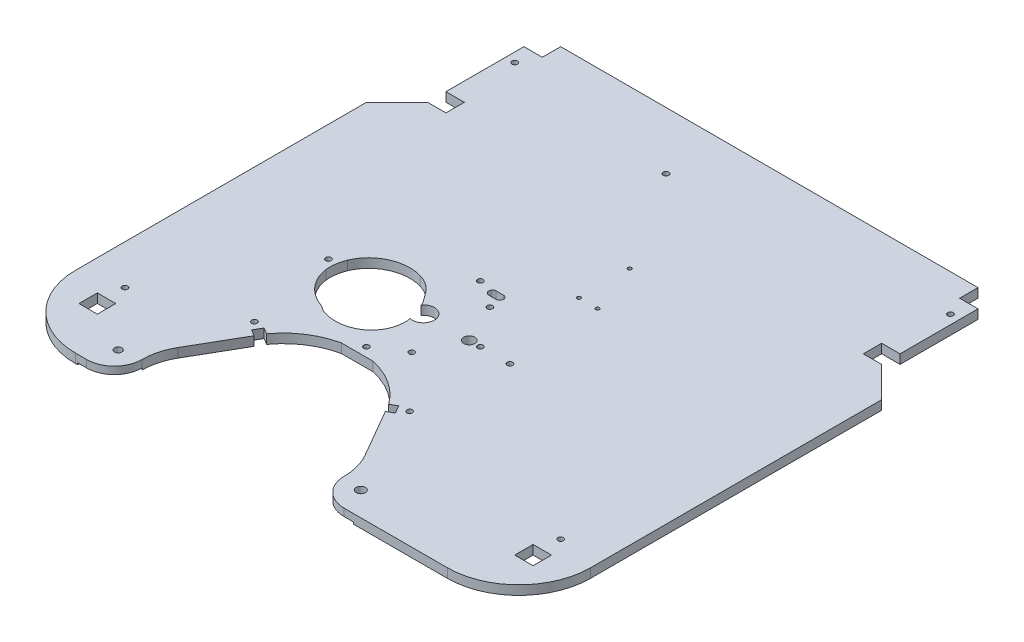
SolidWorks part; units mm, degrees
material "ABS PC"
ref_plane "Plan de face" through (0, 0, 0) normal (0, 0, 1) x (1, 0, 0)
ref_plane "Plan de dessus" through (0, 0, 0) normal (0, 1, 0) x (1, 0, 0)
ref_plane "Plan de droite" through (0, 0, 0) normal (1, 0, 0) x (0, 0, -1)
sketch "Esquisse1" plane through (0, 0, 0) normal (0, 1, 0) x (1, 0, 0)
  line L1 (-140.1, 31.2) -> (140.1, 31.2)
  line L2 (-140.1, 31.2) -> (-140.1, -245.0829)
  line L3 (-140.1, -245.0829) -> (140.1, -245.0829)
  line L4 (140.1, 31.2) -> (140.1, -245.0829)
  line L5 (45, -245.0829) -> (50, -245.0829) construction
  line L6 (-114.5, 31.2) -> (114.5, 31.2) construction
  line L7 (140.1, -4) -> (140.1, 4) construction
  line L8 (-140.1, 4) -> (-140.1, -4) construction
extrude "Boss.-Extru.1" add sketch "Esquisse1" along normal blind 5
sketch "Esquisse2" plane through (0, 0, 0) normal (0, 1, 0) x (1, 0, 0)
  line L3 (-58.1815, -184) -> (-61.6457, -182)
  line L4 (-61.6457, -182) -> (-64.1457, -186.3301)
  line L5 (-64.1457, -186.3301) -> (-60.6815, -188.3301)
  line L7 (-25, -132) -> (-25, -245.0829) construction
  line L8 (-58.1815, -184) -> (-60.6815, -188.3301) construction
  line L9 (-62.6323, -132) -> (62.6323, -132) construction
  line L10 (-25, -62.6323) -> (-25, 62.6323) construction
  line L11 (-60.6815, -188.3301) -> (-75.8539, -214.6094)
  line L13 (-58.1815, -184) -> (-54.7174, -186) construction
  line L14 (-25, -168.25) -> (-25, -231.25) construction
  line L16 (140.1, -245.0829) -> (-140.1, -245.0829) construction
  line L17 (-140.1, -245.0829) -> (140.1, -245.0829) construction
  line L18 (8.1815, -184) -> (4.7174, -186) construction
  line L20 (8.1815, -184) -> (10.6815, -188.3301) construction
  line L21 (10.6815, -188.3301) -> (25.8539, -214.6094)
  line L22 (14.1457, -186.3301) -> (10.6815, -188.3301)
  line L23 (11.6457, -182) -> (14.1457, -186.3301)
  line L24 (8.1815, -184) -> (11.6457, -182)
  line L25 (-62.8957, -184.1651) -> (-67.2258, -181.6651) construction
  line L26 (-95, -245.0829) -> (45, -245.0829)
  arc A0 (-95, -245.0829) -> (-86.2863, -217.8734) centre (-95, -230.0829) ccw construction
  arc A1 (8.1815, -184) -> (-58.1815, -184) centre (-25, -208.0829) ccw
  arc A2 (-95, -245.0829) -> (-80, -230.0829) centre (-95, -230.0829) ccw
  arc A4 (-80, -230.0829) -> (-75.8539, -214.6094) centre (-49.0531, -230.0829) cw
  arc A5 (30, -230.0829) -> (25.8539, -214.6094) centre (-0.9469, -230.0829) ccw
  arc A6 (45, -245.0829) -> (30, -230.0829) centre (45, -230.0829) cw
  circle A8 centre (-67.2258, -181.6651) radius 1.5
  circle A10 centre (17.2258, -181.6651) radius 1.5
  dimension "D4" = 41
  dimension "D8" = 5
  dimension "D9" = 3
  dimension "D1" = 4
  dimension "D2" = 52
  dimension "D3" = 37
  dimension "D5" = 90
  dimension "D6" = 5
  dimension "D7" = 30
extrude "Enlèv. mat.-Extru.2" cut sketch "Esquisse2" along normal through all
sketch "Esquisse3" plane through (0, 5, 0) normal (0, 1, 0) x (1, 0, 0)
  line L0 (-30.2198, -127.0596) -> (-26.1089, -139.1328)
  spline S0 degree 3 poles (-37.7914, -122.1402) (-38.0734, -121.8243) (-38.3657, -121.5165) (-38.9965, -120.9381) (-39.3221, -120.6716) (-39.9982, -120.1678) (-40.3476, -119.9323) (-41.0674, -119.4915) (-41.4393, -119.2855) (-41.8168, -119.0963) knots 0 0 0 0 0.25 0.25 0.5 0.5 0.75 0.75 1 1 1 1 construction
  spline S1 degree 3 poles (-32.1541, -129.7487) (-32.3725, -129.4202) (-32.6019, -129.0988) (-33.0628, -128.4574) (-33.2929, -128.1364) (-33.9829, -127.1734) (-34.442, -126.5306) (-35.3645, -125.2486) (-35.8282, -124.6096) (-36.7788, -123.3501) (-37.2654, -122.7294) (-37.7914, -122.1402) knots 0 0 0 0 0.125 0.125 0.25 0.25 0.5 0.5 0.75 0.75 1 1 1 1 construction
  spline S2 degree 3 poles (-35.6619, -154.1946) (-35.0242, -153.7971) (-34.4156, -153.3543) (-33.5487, -152.619) (-33.2665, -152.3609) (-32.7231, -151.8244) (-32.4631, -151.5476) (-31.717, -150.6924) (-31.2669, -150.0877) (-30.6603, -149.1305) (-30.4697, -148.8029) (-30.1129, -148.13) (-29.9465, -147.7839) (-29.4899, -146.7378) (-29.243, -146.0234) (-28.8562, -144.563) (-28.7157, -143.8147) (-28.4532, -141.5381) (-28.491, -140.0256) (-28.7111, -138.5175) knots 0 0 0 0 0.125 0.125 0.1875 0.1875 0.25 0.25 0.375 0.375 0.4375 0.4375 0.5 0.5 0.625 0.625 0.75 0.75 1 1 1 1 construction
  spline S3 degree 3 poles (-35.6619, -154.1946) (-36.3253, -154.608) (-37.0218, -154.968) (-38.4509, -155.5833) (-39.1871, -155.8402) (-40.6929, -156.2533) (-41.4552, -156.4075) (-42.998, -156.615) (-43.7804, -156.6676) (-46.0993, -156.6733) (-47.6259, -156.4799) (-49.5088, -155.9804) (-49.8836, -155.8673) (-50.622, -155.6166) (-50.9867, -155.4786) (-51.7066, -155.1765) (-52.0616, -155.0123) (-52.5826, -154.748) (-52.7564, -154.66) (-53.0886, -154.4564) (-53.2465, -154.3401) (-53.4028, -154.2206) knots 0 0 0 0 0.125 0.125 0.25 0.25 0.375 0.375 0.5 0.5 0.75 0.75 0.8125 0.8125 0.875 0.875 0.9375 0.9375 0.96875 0.96875 1 1 1 1 construction
  spline S4 degree 3 poles (-41.8168, -119.0963) (-42.9717, -118.5173) (-44.1778, -118.0898) (-46.0518, -117.6406) (-46.691, -117.5235) (-47.9689, -117.3572) (-48.6085, -117.3074) (-49.8889, -117.2725) (-50.5296, -117.2869) (-51.8124, -117.3808) (-52.4575, -117.4608) (-54.3583, -117.7944) (-55.5875, -118.1406) (-57.3737, -118.8468) (-57.9613, -119.1147) (-59.1074, -119.714) (-59.6598, -120.0407) (-61.253, -121.1053) (-62.2339, -121.9217) (-63.3433, -123.0959) (-63.5595, -123.3389) (-63.9727, -123.8343) (-64.1705, -124.0875) (-64.7392, -124.8624) (-65.0859, -125.3992) (-65.725, -126.5066) (-66.0166, -127.0778) (-66.4118, -127.9607) (-66.5364, -128.2602) (-66.7677, -128.8619) (-66.8752, -129.1647) (-67.3727, -130.6881) (-67.6417, -131.9376) (-67.7975, -133.5423) (-67.8198, -133.8663) (-67.8456, -134.511) (-67.8492, -134.8322) (-67.832, -135.7928) (-67.7828, -136.429) (-67.6138, -137.6932) (-67.494, -138.3213) (-67.1803, -139.5691) (-66.9857, -140.1898) (-66.3106, -141.9951) (-65.7352, -143.1386) (-64.7029, -144.7728) (-64.3296, -145.3033) (-63.5406, -146.3156) (-63.1238, -146.8009) (-62.2475, -147.7313) (-61.7884, -148.177) (-60.8134, -149.015) (-60.2997, -149.4102) (-59.6532, -149.8941) (-59.524, -149.9912) (-59.2621, -150.18) (-59.1281, -150.2696) (-58.7233, -150.5349) (-58.4482, -150.704) (-57.6091, -151.1904) (-57.0301, -151.4842) (-56.1848, -151.9623) (-55.907, -152.1283) (-55.4954, -152.386) (-55.361, -152.4765) (-55.1045, -152.6783) (-54.9822, -152.7884) (-54.7446, -153.015) (-54.6281, -153.1308) (-54.3929, -153.36) (-54.2744, -153.4736) (-53.9142, -153.8089) (-53.6638, -154.0209) (-53.4028, -154.2206) knots 0 0 0 0 0.0625 0.0625 0.09375 0.09375 0.125 0.125 0.15625 0.15625 0.1875 0.1875 0.25 0.25 0.28125 0.28125 0.3125 0.3125 0.375 0.375 0.390625 0.390625 0.40625 0.40625 0.4375 0.4375 0.46875 0.46875 0.484375 0.484375 0.5 0.5 0.5625 0.5625 0.578125 0.578125 0.59375 0.59375 0.625 0.625 0.65625 0.65625 0.6875 0.6875 0.75 0.75 0.78125 0.78125 0.8125 0.8125 0.84375 0.84375 0.875 0.875 0.882813 0.882813 0.890625 0.890625 0.90625 0.90625 0.9375 0.9375 0.953125 0.953125 0.960938 0.960938 0.96875 0.96875 0.976563 0.976563 0.984375 0.984375 1 1 1 1 construction
  spline S30 degree 3 poles (-26.1089, -139.1328) (-25.957, -141.5638) (-26.2233, -144.068) (-26.9566, -146.3908) knots 0 0 0 0 1 1 1 1
  spline S31 degree 3 poles (-26.9566, -146.3908) (-27.2228, -147.2342) (-27.8831, -148.8893) (-29.2029, -151.171) (-30.8763, -153.2749) (-32.1537, -154.4712) (-32.834, -155.0244) knots 0 0 0 0 0.25 0.5 0.75 1 1 1 1
  spline S32 degree 3 poles (-32.834, -155.0244) (-34.0816, -156.0391) (-36.8741, -157.7375) (-39.9456, -158.6891) (-41.5144, -158.9883) knots 0 0 0 0 0.5 1 1 1 1
  spline S33 degree 3 poles (-41.5144, -158.9883) (-44.1178, -159.4848) (-46.8613, -159.4832) (-49.4654, -158.9908) knots 0 0 0 0 1 1 1 1
  spline S34 degree 3 poles (-49.4654, -158.9908) (-49.952, -158.8988) (-50.9201, -158.6805) (-51.9843, -158.3611) (-52.6895, -158.1153) (-53.0279, -157.9903) (-53.4112, -157.8436) (-53.8185, -157.6386) (-54.1411, -157.4539) (-54.4726, -157.2537) (-54.8017, -157.0368) (-54.9983, -156.9002) (-55.0989, -156.8301) knots 0 0 0 0 0.25 0.5 0.5625 0.625 0.6875 0.75 0.8125 0.875 0.9375 1 1 1 1
  spline S35 degree 3 poles (-55.0989, -156.8301) (-55.3218, -156.6748) (-55.8004, -156.3308) (-56.3372, -156.039) (-57.1153, -155.7047) (-58.1073, -155.2831) (-59.4212, -154.7248) (-60.6952, -154.0815) (-61.7162, -153.4751) (-62.6513, -152.8651) (-64.3061, -151.7169) (-66.4424, -149.811) (-68.6708, -147.1371) (-71.0288, -143.199) (-72.0496, -139.8117) (-72.3207, -137.531) knots 0 0 0 0 0.03125 0.0625 0.09375 0.125 0.1875 0.25 0.28125 0.3125 0.375 0.5 0.625 0.75 1 1 1 1
  spline S36 degree 3 poles (-72.3207, -137.531) (-72.524, -135.8208) (-72.4832, -132.3293) (-71.5647, -128.9796) (-70.9127, -127.3896) knots 0 0 0 0 0.5 1 1 1 1
  spline S37 degree 3 poles (-70.9127, -127.3896) (-70.401, -126.1419) (-69.1411, -123.7476) (-66.5657, -120.5334) (-63.4815, -117.9312) (-59.9208, -115.9009) (-56.1194, -114.5638) (-52.0895, -113.8994) (-48.0382, -113.9466) (-45.3685, -114.4522) (-44.0724, -114.8246) knots 0 0 0 0 0.125 0.25 0.375 0.5 0.625 0.75 0.875 1 1 1 1
  spline S38 degree 3 poles (-44.0724, -114.8246) (-43.1335, -115.0943) (-41.3015, -115.7539) (-39.094, -116.9388) (-37.4723, -118.0859) (-36.3006, -119.1013) (-35.2972, -120.193) (-34.6853, -120.94) (-34.3845, -121.3211) knots 0 0 0 0 0.25 0.5 0.625 0.75 0.875 1 1 1 1
  spline S39 degree 3 poles (-34.3845, -121.3211) (-33.6538, -122.2469) (-32.5988, -123.6857) (-31.2416, -125.568) (-30.5443, -126.5566) (-30.2198, -127.0596) knots 0 0 0 0 0.5 0.75 1 1 1 1
  spline S40 degree 3 poles (-544.0684, -2053.4709) (-13.3203, -329.9447) (2.5957, -129.3013) (-46.0518, -117.6406) (-46.691, -117.5235) (-47.9689, -117.3572) (-48.6085, -117.3074) (-49.8889, -117.2725) (-50.5296, -117.2869) (-51.8124, -117.3808) (-52.4575, -117.4608) (-54.3583, -117.7944) (-55.5875, -118.1406) (-57.3737, -118.8468) (-57.9613, -119.1147) (-59.1074, -119.714) (-59.6598, -120.0407) (-61.253, -121.1053) (-62.2339, -121.9217) (-63.3433, -123.0959) (-63.5595, -123.3389) (-63.9727, -123.8343) (-64.1705, -124.0875) (-64.7392, -124.8624) (-65.0859, -125.3992) (-65.725, -126.5066) (-66.0166, -127.0778) (-66.4118, -127.9607) (-66.5364, -128.2602) (-66.7677, -128.8619) (-66.8752, -129.1647) (-67.3727, -130.6881) (-67.6417, -131.9376) (-67.7975, -133.5423) (-67.8198, -133.8663) (-67.8456, -134.511) (-67.8492, -134.8322) (-67.832, -135.7928) (-67.7828, -136.429) (-67.6138, -137.6932) (-67.494, -138.3213) (-67.1803, -139.5691) (-66.9857, -140.1898) (-66.3106, -141.9951) (-65.7352, -143.1386) (-64.7029, -144.7728) (-64.3296, -145.3033) (-63.5406, -146.3156) (-63.1238, -146.8009) (-62.2475, -147.7313) (-61.7884, -148.177) (-60.8134, -149.015) (-60.2997, -149.4102) (-59.6532, -149.8941) (-59.524, -149.9912) (-59.2621, -150.18) (-59.1281, -150.2696) (-58.7233, -150.5349) (-58.4482, -150.704) (-57.6091, -151.1904) (-57.0301, -151.4842) (-56.1848, -151.9623) (-55.907, -152.1283) (-55.4954, -152.386) (-55.361, -152.4765) (-55.1045, -152.6783) (-54.9822, -152.7884) (-54.7446, -153.015) (-54.6281, -153.1308) (-54.3929, -153.36) (-54.2744, -153.4736) (-26.8241, -179.0197) (131.7308, -54.8381) (1346.14, 1273.1767) knots -2.339844 -2.339844 -2.339844 -2.339844 0.0625 0.0625 0.09375 0.09375 0.125 0.125 0.15625 0.15625 0.1875 0.1875 0.25 0.25 0.28125 0.28125 0.3125 0.3125 0.375 0.375 0.390625 0.390625 0.40625 0.40625 0.4375 0.4375 0.46875 0.46875 0.484375 0.484375 0.5 0.5 0.5625 0.5625 0.578125 0.578125 0.59375 0.59375 0.625 0.625 0.65625 0.65625 0.6875 0.6875 0.75 0.75 0.78125 0.78125 0.8125 0.8125 0.84375 0.84375 0.875 0.875 0.882813 0.882813 0.890625 0.890625 0.90625 0.90625 0.9375 0.9375 0.953125 0.953125 0.960938 0.960938 0.96875 0.96875 0.976563 0.976563 0.984375 0.984375 2.762304 2.762304 2.762304 2.762304 only from (-41.8168, -119.0963) to (-53.4028, -154.2206)
  spline S41 degree 3 poles (-1939.2427, 445.2377) (-11.3915, 5.3531) (-2.0926, -139.9279) (-38.4509, -155.5833) (-39.1871, -155.8402) (-40.6929, -156.2533) (-41.4552, -156.4075) (-42.998, -156.615) (-43.7804, -156.6676) (-46.0993, -156.6733) (-47.6259, -156.4799) (-49.5088, -155.9804) (-49.8836, -155.8673) (-50.622, -155.6166) (-50.9867, -155.4786) (-51.7066, -155.1765) (-52.0616, -155.0123) (-52.5826, -154.748) (-52.7564, -154.66) (-62.008, -148.9921) (-46.7728, -99.7044) (-1052.7685, -1886.2862) knots -6.110057 -6.110057 -6.110057 -6.110057 0.125 0.125 0.25 0.25 0.375 0.375 0.5 0.5 0.75 0.75 0.8125 0.8125 0.875 0.875 0.9375 0.9375 0.96875 0.96875 2.678123 2.678123 2.678123 2.678123 only from (-35.6619, -154.1946) to (-53.4028, -154.2206)
  spline S42 degree 3 poles (805.3246, -1958.3687) (-625.9447, 427.7737) (-104.0787, -212.4384) (-33.5487, -152.619) (-33.2665, -152.3609) (-32.7231, -151.8244) (-32.4631, -151.5476) (-31.717, -150.6924) (-31.2669, -150.0877) (-30.6603, -149.1305) (-30.4697, -148.8029) (-30.1129, -148.13) (-29.9465, -147.7839) (-29.4899, -146.7378) (-29.243, -146.0234) (-28.8562, -144.563) (-28.7157, -143.8147) (-20.1781, -69.7717) (-507.9815, -8.4894) (1948.7508, 124.0064) knots -15.067184 -15.067184 -15.067184 -15.067184 0.125 0.125 0.1875 0.1875 0.25 0.25 0.375 0.375 0.4375 0.4375 0.5 0.5 0.625 0.625 0.75 0.75 12.82174 12.82174 12.82174 12.82174 only from (-35.6619, -154.1946) to (-28.7111, -138.5175)
  spline S43 degree 3 poles (-1678.0425, -1265.3241) (-10.5484, -165.9011) (-20.1896, -146.3733) (-33.0628, -128.4574) (-33.2929, -128.1364) (-33.9829, -127.1734) (-34.442, -126.5306) (-35.3645, -125.2486) (-35.8282, -124.6096) (-54.2717, -100.1715) (-88.436, -89.3419) (-1650.9877, -1303.2795) knots -6.732601 -6.732601 -6.732601 -6.732601 0.125 0.125 0.25 0.25 0.5 0.5 0.75 0.75 10.201277 10.201277 10.201277 10.201277 only from (-32.1541, -129.7487) to (-37.7914, -122.1402)
  spline S44 degree 3 poles (1561.6634, 1077.8271) (-67.121, -199.6011) (-22.5068, -136.058) (-38.9965, -120.9381) (-39.3221, -120.6716) (-39.9982, -120.1678) (-40.3476, -119.9323) (-65.1031, -104.7717) (-144.7605, -156.1255) (1752.928, -999.5442) knots -12.570471 -12.570471 -12.570471 -12.570471 0.25 0.25 0.5 0.5 0.75 0.75 17.69557 17.69557 17.69557 17.69557 only from (-37.7914, -122.1402) to (-41.8168, -119.0963)
extrude "Enlèv. mat.-Extru.3" cut sketch "Esquisse3" against normal through all
sketch "Esquisse4" plane through (0, 5, 0) normal (0, 1, 0) x (1, 0, 0)
  circle A0 centre (19.9, -82.15) radius 1
  circle A1 centre (9.8, -82.15) radius 1
  circle A2 centre (9.8, -54.55) radius 1
  dimension "D1" = 2
extrude "Enlèv. mat.-Extru.4" cut sketch "Esquisse4" against normal through all
sketch "Esquisse5" plane through (0, 5, 0) normal (0, 1, 0) x (1, 0, 0)
  circle A0 centre (22.1224, -132) radius 1.5
  circle A1 centre (-10.0508, -153.25) radius 1.5
  circle A2 centre (-25, -163) radius 1.5
  circle A3 centre (-10.0508, -110.75) radius 1.5
  circle A4 centre (-25, -101) radius 1.5
  circle A5 centre (-76.6, -132) radius 1.5
  circle A6 centre (6, -132) radius 1.5 construction
  circle A7 centre (6, -132) radius 1.5
  circle A8 centre (0, -132) radius 3
  arc A9 (1.5616, -134.5616) -> (1.5616, -129.4384) centre (0, -132) ccw construction
  circle A10 centre (-10.0508, -110.75) radius 1.5 construction
  dimension "D1" = 3
extrude "Enlèv. mat.-Extru.5" cut sketch "Esquisse5" against normal through all
sketch "Esquisse6" plane through (0, 5, 0) normal (0, 1, 0) x (1, 0, 0)
  circle A0 centre (-25, -132) radius 6
  circle A1 centre (-25, -132) radius 5.4 construction
  dimension "D1" = 12
extrude "Enlèv. mat.-Extru.6" cut sketch "Esquisse6" against normal through all
sketch "Esquisse7" plane through (0, 5, 0) normal (0, 1, 0) x (1, 0, 0)
  line L1 (-16, -103.4) -> (-12, -103.4) construction
  line L2 (-16, -101.4) -> (-12, -101.4)
  line L3 (-16, -105.4) -> (-12, -105.4)
  arc A0 (-16, -101.4) -> (-16, -105.4) centre (-16, -103.4) ccw
  arc A6 (-12, -105.4) -> (-12, -101.4) centre (-12, -103.4) ccw
  arc A7 (-11.4091, -103.2958) -> (-12.5909, -103.2958) centre (-12, -103.4) ccw construction
  arc A9 (-15.4091, -103.2958) -> (-16.5909, -103.2958) centre (-16, -103.4) ccw construction
  point P2 (-14, -103.4)
  dimension "D1" = 4
extrude "Enlèv. mat.-Extru.7" cut sketch "Esquisse7" against normal through all
sketch "Esquisse8" plane through (0, 5, 0) normal (0, 1, 0) x (1, 0, 0)
  line L0 (140.1, -245.0829) -> (140.1, 31.2) construction
  line L1 (101.1, -245.0829) -> (140.1, -245.0829)
  line L2 (140.1, -245.0829) -> (140.1, -206.0829)
  line L3 (-140.1, -245.0829) -> (-140.1, -206.0829)
  line L4 (-140.1, 31.2) -> (-140.1, -245.0829) construction
  line L5 (-140.1, -245.0829) -> (-95, -245.0829) construction
  line L6 (-101.1, -245.0829) -> (-140.1, -245.0829)
  arc A0 (140.1, -206.0829) -> (101.1, -245.0829) centre (101.1, -206.0829) cw
  arc A1 (-140.1, -206.0829) -> (-101.1, -245.0829) centre (-101.1, -206.0829) ccw
extrude "Enlèv. mat.-Extru.8" cut sketch "Esquisse8" against normal through all
sketch "Esquisse9" plane through (0, 5, 0) normal (0, 1, 0) x (1, 0, 0)
  line L0 (-113.5, 21.2) -> (-123.5, 21.2) construction
  line L1 (-113.5, 21.2) -> (-113.5, 31.2) construction
  line L2 (-113.5, -31.2) -> (-113.5, -21.2) construction
  line L3 (-113.5, -21.2) -> (-123.5, -21.2) construction
  line L4 (-113.5, -31.2) -> (-123.5, -31.2) construction
  line L5 (-113.5, 21.2) -> (-123.5, 21.2)
  line L6 (-113.5, 21.2) -> (-113.5, 31.2)
  line L7 (-113.5, -31.2) -> (-113.5, -21.2)
  line L8 (-113.5, -21.2) -> (-123.5, -21.2)
  line L9 (-113.5, -31.2) -> (-123.5, -31.2)
  line L10 (-123.5, -21.2) -> (-123.5, 21.2)
  line L11 (-123.5, -31.2) -> (-140.1, -47.8)
  line L12 (-140.1, 31.2) -> (-140.1, -206.0829) construction
  line L13 (-140.1, -47.8) -> (-140.1, 31.2)
  line L14 (-140.1, 31.2) -> (-113.5, 31.2)
  line L15 (0, 0) -> (0, 79.4635) construction
  line L16 (140.1, 31.2) -> (113.5, 31.2)
  line L17 (140.1, -47.8) -> (140.1, 31.2)
  line L18 (123.5, -31.2) -> (140.1, -47.8)
  line L19 (123.5, -21.2) -> (123.5, 21.2)
  line L20 (113.5, -31.2) -> (123.5, -31.2)
  line L21 (113.5, -21.2) -> (123.5, -21.2)
  line L22 (113.5, -31.2) -> (113.5, -21.2)
  line L23 (113.5, 21.2) -> (113.5, 31.2)
  line L24 (113.5, 21.2) -> (123.5, 21.2)
  dimension "D1" = 45
extrude "Enlèv. mat.-Extru.9" cut sketch "Esquisse9" against normal through all
sketch "Esquisse10" plane through (0, 0, 0) normal (0, -1, 0) x (1, 0, 0)
  line L1 (-100, 245.0829) -> (-100, 242.0829) construction
  line L2 (-95, 242.0829) -> (-100, 242.0829) construction
  line L4 (45, 242.0829) -> (50, 242.0829) construction
  line L5 (50, 242.0829) -> (50, 245.0829)
  line L6 (50, 245.0829) -> (45, 245.0829)
  line L7 (45, 242.0829) -> (50, 242.0829)
  line L8 (50, 245.0829) -> (50, 242.0829) construction
  line L9 (-101.1, 245.0829) -> (-95, 245.0829) construction
  line L11 (45, 245.0829) -> (50, 245.0829) construction
  line L20 (-95, 245.0829) -> (-100, 245.0829)
  line L21 (-100, 245.0829) -> (-100, 242.0829)
  line L22 (-100, 242.0829) -> (-95, 242.0829)
  arc A0 (-88.029, 220.3153) -> (-25, 23.5) centre (-25, 132) ccw construction
  arc A1 (-86.2863, 217.8734) -> (-25, 26.5) centre (-25, 132) ccw construction
  arc A2 (-25, 26.5) -> (50, 206.1974) centre (-25, 132) ccw construction
  arc A3 (-25, 23.5) -> (50, 210.4044) centre (-25, 132) ccw construction
  arc A4 (-88.029, 220.3153) -> (-25, 23.5) centre (-25, 132) ccw
  arc A5 (-86.2863, 217.8734) -> (-25, 26.5) centre (-25, 132) ccw
  arc A6 (-25, 26.5) -> (36.2863, 217.8734) centre (-25, 132) ccw
  arc A7 (-25, 23.5) -> (38.029, 220.3153) centre (-25, 132) ccw
  arc A8 (45, 245.0829) -> (36.2863, 217.8734) centre (45, 230.0829) ccw construction
  arc A10 (45, 245.0829) -> (36.2863, 217.8734) centre (45, 230.0829) ccw
  arc A11 (45, 242.0829) -> (38.029, 220.3153) centre (45, 230.0829) ccw
  arc A12 (45, 242.0829) -> (38.029, 220.3153) centre (45, 230.0829) ccw construction
  arc A14 (-88.029, 220.3153) -> (-95, 242.0829) centre (-95, 230.0829) ccw construction
  arc A15 (-80, 230.0829) -> (-95, 245.0829) centre (-95, 230.0829) ccw construction
  arc A16 (-86.2863, 217.8734) -> (-95, 245.0829) centre (-95, 230.0829) ccw
  arc A17 (-88.029, 220.3153) -> (-95, 242.0829) centre (-95, 230.0829) ccw
extrude "Enlèv. mat.-Extru.10" cut sketch "Esquisse10" against normal blind 1
sketch "Esquisse11" plane through (0, 5, 0) normal (0, 1, 0) x (1, 0, 0)
  line L4 (-123.5, -210.8) -> (-123.5, -220.8)
  line L5 (-113.5, -210.8) -> (-123.5, -210.8)
  line L6 (-113.5, -220.8) -> (-113.5, -210.8)
  line L7 (-123.5, -220.8) -> (-113.5, -220.8)
  line L8 (-123.5, -210.8) -> (-123.5, -220.8)
  line L9 (-113.5, -210.8) -> (-123.5, -210.8)
  line L10 (-113.5, -220.8) -> (-113.5, -210.8)
  line L11 (-123.5, -220.8) -> (-113.5, -220.8)
  line L12 (113.5, -210.8) -> (113.5, -220.8)
  line L13 (123.5, -210.8) -> (113.5, -210.8)
  line L14 (123.5, -220.8) -> (123.5, -210.8)
  line L15 (113.5, -220.8) -> (123.5, -220.8)
  line L16 (113.5, -210.8) -> (113.5, -220.8)
  line L17 (123.5, -210.8) -> (113.5, -210.8)
  line L18 (123.5, -220.8) -> (123.5, -210.8)
  line L19 (113.5, -220.8) -> (123.5, -220.8)
  dimension "D1" = 0
  dimension "D2" = 0
extrude "Enlèv. mat.-Extru.11" cut sketch "Esquisse11" against normal through all
sketch "Esquisse12" plane through (0, 5, 0) normal (0, 1, 0) x (1, 0, 0)
  circle A0 centre (41, -232) radius 2.5 construction
  circle A1 centre (41, -232) radius 2.5
  circle A2 centre (-91, -232) radius 2 construction
  circle A3 centre (-91, -232) radius 2
extrude "Enlèv. mat.-Extru.12" cut sketch "Esquisse12" against normal through all
sketch "Esquisse13" plane through (0, 5, 0) normal (0, 1, 0) x (1, 0, 0)
  circle A0 centre (-118.5, -200.8) radius 1.5
  circle A1 centre (-118.5, 11.2) radius 1.5
  circle A2 centre (-118.5, 11.2) radius 1.525 construction
  circle A3 centre (-118.5, -200.8) radius 1.525 construction
  circle A4 centre (118.5, 11.2) radius 1.5
  circle A5 centre (118.5, -200.8) radius 1.5
  circle A6 centre (118.5, -200.8) radius 1.25 construction
  circle A7 centre (-25, 0) radius 1.5
  circle A9 centre (-25, 0) radius 1.5 construction
  dimension "D1" = 3
extrude "Enlèv. mat.-Extru.15" cut sketch "Esquisse13" against normal through all
sketch "Esquisse14" plane through (0, 0, 0) normal (0, -1, 0) x (1, 0, 0)
  line L0 (-115.5, 168) -> (115.5, 168) construction
  line L1 (-33.6234, 168) -> (-16.3766, 168)
  line L2 (-33.6234, 168) -> (-33.6234, 166)
  line L3 (-33.6234, 166) -> (-16.3766, 166)
  line L4 (-16.3766, 168) -> (-16.3766, 166)
  arc A0 (-58.1815, 184) -> (8.1815, 184) centre (-25, 208.0829) ccw construction
  dimension "D1" = 17.2468
  dimension "D2" = 2
extrude "Boss.-Extru.2" add sketch "Esquisse14" against normal up to surface (5 mm away) up to face at (-25, 5, 1.5)
